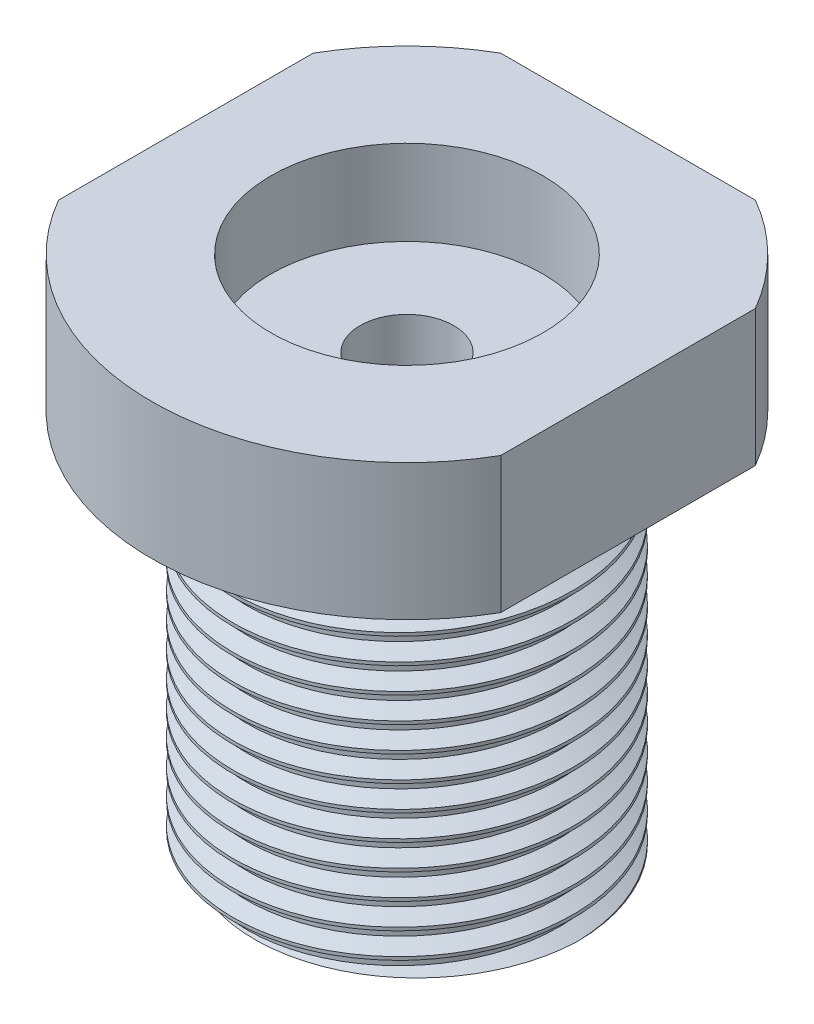
SolidWorks part; units mm, degrees
ref_plane "Front Plane" through (0, 0, 0) normal (0, 0, 1) x (1, 0, 0)
ref_plane "Top Plane" through (0, 0, 0) normal (0, 1, 0) x (1, 0, 0)
ref_plane "Right Plane" through (0, 0, 0) normal (1, 0, 0) x (0, 0, -1)
sketch "Sketch1" plane through (0, 0, 0) normal (1, 0, 0) x (0, 0, -1)
  line L2 (15, 30) -> (15, 22)
  line L3 (15, 22) -> (10, 22)
  line L4 (10, 22) -> (10, 0)
  line L6 (0, 0) -> (0, 30) construction
  line L7 (15, 30) -> (8, 30)
  line L8 (8, 30) -> (8, 25)
  line L9 (8, 25) -> (2.75, 25)
  line L10 (2.75, 25) -> (2.75, 5)
  line L11 (2.75, 5) -> (8, 5)
  line L12 (8, 5) -> (8, 0)
  line L13 (8, 0) -> (10, 0)
  dimension "D1" = 8
  dimension "D2" = 5.5
  dimension "D3" = 5
  dimension "D4" = 15
  dimension "D5" = 8
  dimension "D6" = 30
  dimension "D7" = 10
  dimension "D8" = 20
revolve "Revolve1" add sketch "Sketch1" angle 360 about L6
thread "Thread1" pitch 1.5 method cut profile "Thread Profile1" start angle 0, offset 3, length 26, pitch 1.5, diameter 20
ref_plane "Plane1" through (10, -3, 0) normal (0, 0, 1) x (1, 0, 0)
sketch "Thread Profile1" plane through (10, -3, 0) normal (0, 0, 1) x (1, 0, 0)
  line L0 (0, 0) -> (0, 1.5) construction
  line L11 (0, 0) -> (0, 1.3125)
  line L12 (0, 1.3125) -> (-0.8119, 0.8437)
  line L13 (-0.8119, 0.8437) -> (-0.8119, 0.4687)
  line L15 (-0.8119, 0.4687) -> (0, 0)
  line L17 (-0.8119, 0.6562) -> (0, 0.6562) construction
  point P2 (0, 0)
  dimension "Pitch" = 1.5
  dimension "Profile_Angle" = 60
  dimension "Profile_Land" = 0.375
  dimension "Profile_Height" = 0.8119
sketch "Sketch2" plane through (0, 30, 0) normal (0, 1, 0) x (1, 0, 0)
  line L0 (13, 7.4833) -> (13, -7.4833)
  line L1 (0, 0) -> (0, 15) construction
  line L2 (0, 0) -> (10.6066, 10.6066) construction
  line L3 (7.4833, 13) -> (-7.4833, 13)
  line L4 (-13, 7.4833) -> (-13, -7.4833)
  circle A0 centre (0, 0) radius 15 construction
  arc A1 (-7.4833, 13) -> (7.4833, 13) centre (0, 0) cw
  circle A2 centre (0, 0) radius 15
  arc A3 (13, -7.4833) -> (13, 7.4833) centre (0, 0) ccw
  arc A4 (-13, -7.4833) -> (-13, 7.4833) centre (0, 0) cw
  dimension "D1" = 13
  dimension "D3" = 45
  dimension "D2" = 0
extrude "Cut-Extrude1" cut sketch "Sketch2" against normal blind 22
sketch "Sketch3" plane through (0, 0, -13) normal (0, 0, -1) x (-1, 0, 0)
  line L0 (0, 0) -> (0, 26) construction
  line L1 (-7.4833, 30) -> (-7.4833, 22) construction
  circle A0 centre (0, 26) radius 1.5
  point P6 (-7.4833, 26)
  dimension "D1" = 3
extrude "Cut-Extrude2" cut sketch "Sketch3" against normal blind 4
